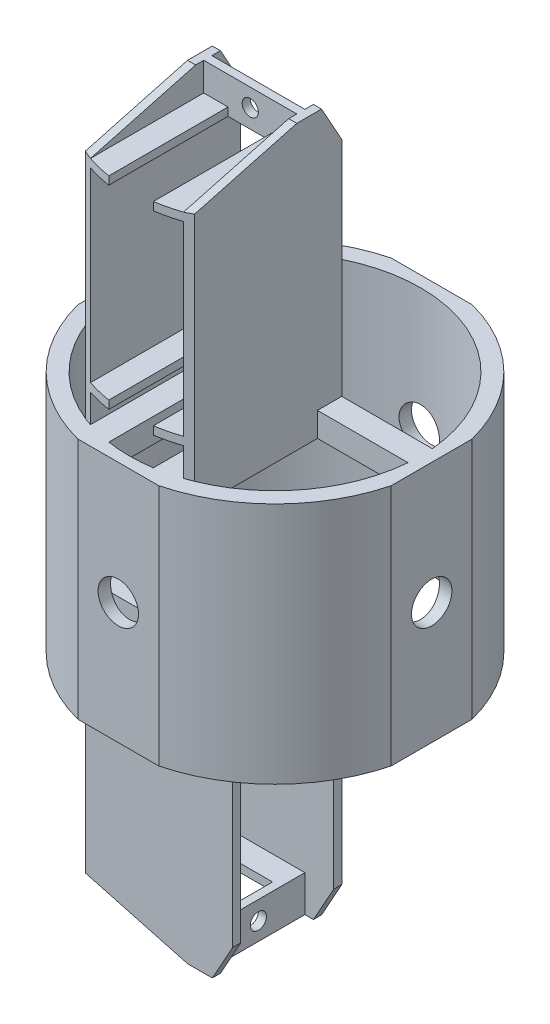
SolidWorks part; units mm, degrees
material "聚脂树脂"
ref_plane "前视基准面" through (0, 0, 0) normal (0, 0, 1) x (1, 0, 0)
ref_plane "上视基准面" through (0, 0, 0) normal (0, 1, 0) x (1, 0, 0)
ref_plane "右视基准面" through (0, 0, 0) normal (1, 0, 0) x (0, 0, -1)
other "Configuration Table"
sketch "草图3" plane through (0, 0, 0) normal (0, 1, 0) x (1, 0, 0)
  circle A0 centre (0, 0) radius 20
  circle A1 centre (0, 0) radius 18
  dimension "D1" = 40
  dimension "D2" = 36
extrude "凸台-拉伸2" add sketch "草图3" along normal blind 30
sketch "草图5" plane through (0, 0, 0) normal (0, 1, 0) x (1, 0, 0)
  line L0 (-1000, 0) -> (49000, 0) construction
  line L1 (0, -1000) -> (0, 49000) construction
  line L2 (-19.3649, -5) -> (-19.3649, 5)
  line L3 (-707.1068, -707.1068) -> (34648.2323, 34648.2323) construction
  line L4 (707.1068, -707.1068) -> (-34648.2323, 34648.2323) construction
  line L5 (19.3649, -5) -> (19.3649, 5)
  line L6 (-5, 19.3649) -> (5, 19.3649)
  line L7 (-5, -19.3649) -> (5, -19.3649)
  circle A0 centre (0, 0) radius 18 construction
  circle A1 centre (0, 0) radius 20 construction
  circle A2 centre (0, 0) radius 18
  circle A3 centre (0, 0) radius 20
  point P13 (-19.3649, 0)
  dimension "D1" = 10
sketch "草图6" plane through (0, 0, 0) normal (0, 1, 0) x (1, 0, 0)
  line L0 (-1000, 0) -> (49000, 0) construction
  line L1 (0, -1000) -> (0, 49000) construction
  line L2 (-707.1068, -707.1068) -> (34648.2323, 34648.2323) construction
  line L3 (707.1068, -707.1068) -> (-34648.2323, 34648.2323) construction
  line L4 (-17.2916, -5) -> (-17.2916, 5)
  line L5 (-5, -17.2916) -> (5, -17.2916)
  line L6 (5, 17.2916) -> (-5, 17.2916)
  line L7 (17.2916, 5) -> (17.2916, -5)
  circle A0 centre (0, 0) radius 18 construction
  circle A1 centre (0, 0) radius 18
  circle A2 centre (0, 0) radius 20 construction
  circle A3 centre (0, 0) radius 20
  point P17 (-17.2916, 0)
  dimension "D1" = 10
sketch "草图11" plane through (0, 0, 0) normal (0, 0, 1) x (1, 0, 0)
  line L0 (20, 30) -> (-20, 0) construction
  line L1 (-20, 30) -> (20, 0) construction
  circle A0 centre (0, 15) radius 2.5
  dimension "D1" = 5
extrude "切除-拉伸5" cut sketch "草图11" against normal through all and the other way blind 40
sketch "草图12" plane through (0, 0, 0) normal (1, 0, 0) x (0, 0, -1)
  line L0 (20, 30) -> (-20, 0) construction
  line L1 (20, 0) -> (-20, 30) construction
  circle A0 centre (0, 15) radius 2.5
  dimension "D1" = 5
extrude "切除-拉伸6" cut sketch "草图12" against normal through all and the other way blind 40
sketch "草图22" plane through (0, 0, 0) normal (0, 1, 0) x (1, 0, 0)
  line L0 (0, -1000) -> (0, 49000) construction
  line L1 (-1.5, 0) -> (1.5, 0) construction
  line L2 (1.5, 17.9374) -> (1.5, -17.9374)
  line L3 (-1.5, 17.9374) -> (-1.5, -17.9374)
  circle A0 centre (0, 0) radius 18
  point P8 (0, 0)
  point P10 (1.5, 0)
  point P14 (-1.5, 0)
  dimension "D1" = 36
  dimension "D2" = 3
extrude "凸台-拉伸13" add sketch "草图22" along normal blind 3 contours L2 A0 L3 region at (0, 0, 0)
sketch "草图23" plane through (0, 0, 0) normal (0, 1, 0) x (1, 0, 0)
  line L0 (-1000, 0) -> (49000, 0) construction
  line L2 (1.5, 17.9374) -> (1.5, -17.9374) construction
  line L3 (1.5, 17.9374) -> (1.5, -17.9374)
  line L5 (-16.6864, -6.75) -> (1.5, -6.75)
  line L6 (-16.6864, 6.75) -> (1.5, 6.75)
  circle A0 centre (0, 0) radius 18
  point P12 (-16.6864, 0)
  dimension "D1" = 36
  dimension "D2" = 13.5
  dimension "D3" = 18.1864
  dimension "D4" = 13.5
extrude "凸台-拉伸14" add sketch "草图23" along normal blind 3 contours A0 L0 L3 L6 | L0 A0 L5 L3 region at (-8.0383, 0, -3.3366) region at (-8.0383, 0, 3.3366)
sketch "草图44" plane through (0, 0, 0) normal (0, 1, 0) x (1, 0, 0)
  line L0 (0, 1.5) -> (0, -1.5) construction
  line L1 (17.9374, 1.5) -> (-17.9374, 1.5)
  line L2 (-17.9374, -1.5) -> (17.9374, -1.5)
  arc A0 (-17.9374, 1.5) -> (-17.9374, -1.5) centre (0, 0) ccw
  arc A1 (17.9374, -1.5) -> (17.9374, 1.5) centre (0, 0) ccw
  point P5 (0, 0)
  point P9 (0, 1.5)
  point P12 (0, -1.5)
  dimension "D1" = 36
  dimension "D2" = 3
extrude "凸台-拉伸26" add sketch "草图44" against normal blind 3 from surface starting at face at (0, 30, 20)
sketch "草图45" plane through (0, 0, 0) normal (0, 1, 0) x (1, 0, 0)
  line L0 (0, -1000) -> (0, 49000) construction
  line L5 (-17.9374, 1.5) -> (17.9374, 1.5) construction
  line L6 (-6.75, 1.5) -> (6.75, 1.5)
  line L7 (6.75, -16.6864) -> (6.75, 1.5)
  line L8 (-6.75, -16.6864) -> (-6.75, 1.5)
  arc A0 (-6.75, -16.6864) -> (6.75, -16.6864) centre (0, 0) ccw
  point P9 (0, -16.6864)
  dimension "D1" = 13.5
  dimension "D2" = 18.1864
extrude "凸台-拉伸27" add sketch "草图45" against normal blind 3 from surface starting at face at (0, 30, -9.75)
sketch "草图54" plane through (0, 0, 0) normal (0, 1, 0) x (1, 0, 0)
  line L0 (0, -1000) -> (0, 49000) construction
  line L2 (-5.75, -17.0569) -> (-5.75, -3.0569)
  line L3 (-5.75, -3.0569) -> (5.75, -3.0569)
  line L4 (5.75, -3.0569) -> (5.75, -17.0569)
  line L5 (-6.75, -2.0569) -> (-6.75, -16.6864)
  line L6 (-6.75, -16.6864) -> (-6.75, -1.5) construction
  line L8 (6.75, -2.0569) -> (6.75, -16.6864)
  line L9 (6.75, -1.5) -> (6.75, -16.6864) construction
  line L11 (6.75, -2.0569) -> (-6.75, -2.0569)
  arc A0 (-6.75, -16.6864) -> (-5.75, -17.0569) centre (0, 0) ccw
  arc A1 (5.75, -17.0569) -> (6.75, -16.6864) centre (0, 0) ccw
  arc A2 (-6.75, -16.6864) -> (-5.75, -17.0569) centre (0, 0) ccw
  point P9 (0, -17.0569)
  dimension "D1" = 11.5
  dimension "D2" = 13.5
  dimension "D3" = 14
  dimension "D4" = 1
  dimension "D5" = 2.0569
extrude "凸台-拉伸32" add sketch "草图54" along normal blind 32 from surface contours L0 L3 L4 A1 L8 L11 | L3 L0 L11 L5 A0 L2 region at (-2.875, 0, 2.8924) region at (0.1645, 0, 2.5569) starting at face at (11.1953, 30, 7.0897)
sketch "草图55" plane through (0, 0, 0) normal (0, 0, 1) x (1, 0, 0)
  line L0 (-6.75, 62) -> (6.75, 30) construction
  line L1 (-6.75, 30) -> (6.75, 62) construction
  line L2 (0, 59.8) -> (0, 32.2) construction
  line L4 (5.75, 57.5) -> (-5.75, 57.5)
  line L5 (5.75, 57.5) -> (5.75, 34.5)
  line L6 (5.75, 34.5) -> (-5.75, 34.5)
  line L7 (-5.75, 57.5) -> (-5.75, 34.5)
  line L8 (5.75, 57.5) -> (-5.75, 34.5) construction
  line L9 (5.75, 34.5) -> (-5.75, 57.5) construction
  circle A0 centre (0, 59.8) radius 1
  circle A1 centre (0, 32.2) radius 1
  point P6 (0, 46)
  point P12 (0, 46)
  dimension "D4" = 2
  dimension "D5" = 2
  dimension "D1" = 27.6
  dimension "D2" = 23
  dimension "D3" = 11.5
extrude "切除-拉伸25" cut sketch "草图55" along normal blind 32
sketch "草图56" plane through (0, 0, 0) normal (0, 1, 0) x (1, 0, 0)
  line L0 (-2.0569, -6.75) -> (-16.6864, -6.75)
  line L1 (-16.6864, -6.75) -> (-1.5, -6.75) construction
  line L2 (0, 0) -> (-28.8356, 0) construction
  line L4 (-2.0569, -6.75) -> (-2.0569, 6.75)
  line L5 (-16.6864, 6.75) -> (-1.5, 6.75) construction
  line L6 (-17.0569, 5.75) -> (-3.0569, 5.75)
  line L7 (-3.0569, 5.75) -> (-3.0569, -5.75)
  line L8 (-3.0569, -5.75) -> (-17.0569, -5.75)
  line L9 (-2.0569, 6.75) -> (-16.6864, 6.75)
  arc A0 (-16.6864, 6.75) -> (-17.0569, 5.75) centre (0, 0) ccw
  arc A1 (-17.0569, -5.75) -> (-16.6864, -6.75) centre (0, 0) ccw
  point P13 (-17.0569, 0)
  dimension "D1" = 11.5
  dimension "D2" = 14
  dimension "D3" = 1
  dimension "D4" = 1
extrude "凸台-拉伸33" add sketch "草图56" against normal blind 32
sketch "草图57" plane through (0, 0, 0) normal (1, 0, 0) x (0, 0, -1)
  line L0 (6.75, 0) -> (-6.75, -32) construction
  line L1 (6.75, -32) -> (-6.75, 0) construction
  line L2 (0, -29.8) -> (0, -2.2) construction
  line L4 (-5.75, -4.5) -> (5.75, -4.5)
  line L5 (-5.75, -4.5) -> (-5.75, -27.5)
  line L6 (-5.75, -27.5) -> (5.75, -27.5)
  line L7 (5.75, -4.5) -> (5.75, -27.5)
  line L8 (-5.75, -4.5) -> (5.75, -27.5) construction
  line L9 (-5.75, -27.5) -> (5.75, -4.5) construction
  circle A0 centre (0, -2.2) radius 1
  circle A1 centre (0, -29.8) radius 1
  point P8 (0, -16)
  point P12 (0, -16)
  dimension "D4" = 2
  dimension "D5" = 2
  dimension "D1" = 27.6
  dimension "D2" = 23
  dimension "D3" = 11.5
extrude "切除-拉伸26" cut sketch "草图57" against normal blind 32
sketch "草图59" plane through (0, 0, 0) normal (0, 1, 0) x (1, 0, 0)
  line L0 (-6.75, -2.0569) -> (-6.75, 1.5)
  line L1 (-17.9374, 1.5) -> (17.9374, 1.5) construction
  line L2 (-6.75, 1.5) -> (-5.75, 1.5)
  line L3 (-5.75, 1.5) -> (-5.75, -2.0569)
  line L4 (-6.75, -2.0569) -> (6.75, -2.0569) construction
  line L5 (-5.75, -2.0569) -> (-6.75, -2.0569)
  line L6 (6.75, -2.0569) -> (6.75, 1.5)
  line L7 (6.75, 1.5) -> (5.75, 1.5)
  line L8 (5.75, 1.5) -> (5.75, -2.0569)
  line L9 (6.75, -2.0569) -> (5.75, -2.0569)
  dimension "D1" = 1
  dimension "D2" = 1
extrude "凸台-拉伸34" add sketch "草图59" along normal up to surface (62 mm away) from surface up to face at (0, 62, 9.7161) starting at face at (0, 30, 7.2412)
sketch "草图60" plane through (0, 0, 0) normal (0, 1, 0) x (1, 0, 0)
  line L0 (-2.0569, -6.75) -> (1.5, -6.75)
  line L1 (1.5, 17.9374) -> (1.5, -17.9374) construction
  line L2 (1.5, -6.75) -> (1.5, -5.75)
  line L3 (1.5, -5.75) -> (-2.0569, -5.75)
  line L4 (-2.0569, -6.75) -> (-2.0569, 6.75) construction
  line L5 (-2.0569, -5.75) -> (-2.0569, -6.75)
  line L6 (-2.0569, 6.75) -> (1.5, 6.75)
  line L7 (1.5, 6.75) -> (1.5, 5.75)
  line L8 (1.5, 5.75) -> (-2.0569, 5.75)
  line L9 (-2.0569, 5.75) -> (-2.0569, 6.75)
  dimension "D1" = 1
  dimension "D2" = 1
extrude "凸台-拉伸35" add sketch "草图60" against normal up to surface (32 mm away) from surface up to face at (-9.7161, -32, 0) starting at face at (-7.2412, 0, 0)
sketch "草图62" plane through (0, 0, 0) normal (1, 0, 0) x (0, 0, -1)
  line L0 (1.5, 62) -> (1.5, 57.5)
  line L1 (1.5, 62) -> (1.5, 30) construction
  line L2 (1.5, 57.5) -> (-1, 62)
  line L3 (-16.6864, 62) -> (1.5, 62) construction
  line L4 (-1, 62) -> (1.5, 62)
  line L5 (-17.0569, 62) -> (-4.0569, 62)
  line L6 (-4.0569, 62) -> (-17.0569, 58.5)
  line L7 (-17.0569, 62) -> (-17.0569, 30) construction
  line L8 (-17.0569, 58.5) -> (-17.0569, 62)
  dimension "D1" = 2.5
  dimension "D2" = 4.5
  dimension "D3" = 3.5
  dimension "D4" = 13
extrude "切除-拉伸27" cut sketch "草图62" against normal through all and the other way through all contours L8 L5 L6 | L4 L0 L2
sketch "草图63" plane through (0, 0, 0) normal (0, 0, 1) x (1, 0, 0)
  line L0 (1.5, -32) -> (1.5, -27.5)
  line L1 (1.5, -32) -> (1.5, 0) construction
  line L2 (1.5, -27.5) -> (-1, -32)
  line L3 (-16.6864, -32) -> (1.5, -32) construction
  line L4 (-1, -32) -> (1.5, -32)
  line L5 (-17.0569, -32) -> (-4.0569, -32)
  line L6 (-4.0569, -32) -> (-17.0569, -28.5)
  line L7 (-17.0569, -32) -> (-17.0569, 0) construction
  line L8 (-17.0569, -28.5) -> (-17.0569, -32)
  dimension "D1" = 4.5
  dimension "D2" = 2.5
  dimension "D3" = 13
  dimension "D4" = 3.5
extrude "切除-拉伸28" cut sketch "草图63" against normal through all and the other way through all
sketch "草图64" plane through (0, 0, 0) normal (0, 1, 0) x (1, 0, 0)
  line L0 (-5.75, -3.0569) -> (-2.75, -3.0569)
  line L1 (5.75, -3.0569) -> (-5.75, -3.0569) construction
  line L2 (-2.75, -3.0569) -> (-2.75, -17.7887)
  line L3 (-5.75, -3.0569) -> (-5.75, -17.0569)
  line L4 (5.75, -17.0569) -> (5.75, -3.0569)
  line L5 (5.75, -3.0569) -> (2.75, -3.0569)
  line L6 (5.75, -3.0569) -> (-5.75, -3.0569) construction
  line L7 (2.75, -3.0569) -> (2.75, -17.7887)
  arc A0 (-5.75, -17.0569) -> (-2.75, -17.7887) centre (0, 0) ccw
  arc A1 (2.75, -17.7887) -> (5.75, -17.0569) centre (0, 0) ccw
  dimension "D1" = 3
  dimension "D2" = 3
extrude "凸台-拉伸36" add sketch "草图64" against normal blind 1 from surface contours L3 A0 L2 L0 | L4 L5 L7 A1 starting at face at (0, 34.5, 2.5569)
sketch "草图65" plane through (0, 0, 0) normal (0, 1, 0) x (1, 0, 0)
  line L0 (-17.0569, -5.75) -> (-3.0569, -5.75)
  line L1 (-3.0569, -5.75) -> (-3.0569, -2.75)
  line L2 (-3.0569, 5.75) -> (-3.0569, -5.75) construction
  line L3 (-3.0569, -2.75) -> (-17.7887, -2.75)
  line L4 (-17.0569, 5.75) -> (-3.0569, 5.75)
  line L5 (-3.0569, 5.75) -> (-3.0569, 2.75)
  line L6 (-3.0569, 2.75) -> (-17.7887, 2.75)
  arc A0 (-17.7887, -2.75) -> (-17.0569, -5.75) centre (0, 0) ccw
  arc A1 (-17.0569, 5.75) -> (-17.7887, 2.75) centre (0, 0) ccw
  dimension "D1" = 3
  dimension "D2" = 3
extrude "凸台-拉伸37" add sketch "草图65" along normal blind 1 from surface starting at face at (-2.5569, -4.5, 0)
sketch "草图66" plane through (0, 0, 0) normal (0, 1, 0) x (1, 0, 0)
  line L0 (-5.75, -3.0569) -> (5.75, -3.0569)
  line L1 (5.75, -3.0569) -> (5.75, -17.0569)
  line L2 (-5.75, -3.0569) -> (-5.75, -17.0569)
  arc A0 (-5.75, -17.0569) -> (5.75, -17.0569) centre (0, 0) ccw
extrude "凸台-拉伸38" add sketch "草图66" along normal blind 1 from surface starting at face at (0, 57.5, 2.5569)
sketch "草图67" plane through (0, 0, 0) normal (0, 1, 0) x (1, 0, 0)
  line L0 (-17.0569, -5.75) -> (-3.0569, -5.75)
  line L1 (-17.0569, -5.75) -> (-2.0569, -5.75) construction
  line L2 (-17.0569, -5.75) -> (-4.0569, -5.75) construction
  line L3 (-3.0569, -5.75) -> (-3.0569, 5.75)
  line L4 (-3.0569, 5.75) -> (-17.0569, 5.75)
  arc A0 (-17.0569, 5.75) -> (-17.0569, -5.75) centre (0, 0) ccw
extrude "凸台-拉伸39" add sketch "草图67" against normal blind 1 from surface starting at face at (-2.5569, -27.5, 0)
sketch "草图68" plane through (0, 0, 0) normal (0, 1, 0) x (1, 0, 0)
  line L1 (5.75, -3.0569) -> (-5.75, -3.0569) construction
  line L2 (2.75, -3.0569) -> (-2.75, -3.0569)
  arc A0 (-2.75, -3.0569) -> (2.75, -3.0569) centre (0, -3.0569) ccw
  dimension "D1" = 5.5
extrude "切除-拉伸29" cut sketch "草图68" against normal blind 1 from surface starting at face at (0, 58.5, 10.2927)
sketch "草图69" plane through (0, 0, 0) normal (0, 1, 0) x (1, 0, 0)
  line L1 (-3.0569, 5.75) -> (-3.0569, -5.75) construction
  line L2 (-3.0569, -2.75) -> (-3.0569, 2.75)
  arc A0 (-3.0569, 2.75) -> (-3.0569, -2.75) centre (-3.0569, 0) ccw
  dimension "D1" = 5.5
extrude "切除-拉伸30" cut sketch "草图69" along normal blind 1 from surface starting at face at (-10.2927, -28.5, 0)
sketch "草图70" plane through (0, 0, 0) normal (0, 1, 0) x (1, 0, 0)
  line L0 (-2.75, -3.0569) -> (-2.75, -17.7887)
  line L1 (-2.75, -3.0569) -> (2.75, -3.0569)
  line L2 (2.75, -3.0569) -> (2.75, -17.7887)
  arc A0 (-2.75, -17.7887) -> (2.75, -17.7887) centre (0, 0) ccw
extrude "切除-拉伸31" cut sketch "草图70" against normal blind 3 from surface starting at face at (0, 30, 0.2784)
sketch "草图71" plane through (0, 0, 0) normal (0, 1, 0) x (1, 0, 0)
  line L0 (-17.7887, 2.75) -> (-3.0569, 2.75)
  line L1 (-3.0569, 2.75) -> (-3.0569, -2.75)
  line L2 (-3.0569, 5.75) -> (-3.0569, -5.75) construction
  line L3 (-3.0569, -2.75) -> (-17.7887, -2.75)
  arc A0 (-17.7887, 2.75) -> (-17.7887, -2.75) centre (0, 0) ccw
  arc A1 (-3.0569, 2.75) -> (-3.0569, -2.75) centre (-3.0569, 0) ccw construction
extrude "切除-拉伸32" cut sketch "草图71" along normal blind 3
sketch "草图74" plane through (0, 0, 0) normal (0, 1, 0) x (1, 0, 0)
  line L0 (-2.75, -3.0569) -> (-2.75, -17.7887)
  line L1 (-2.75, -3.0569) -> (2.75, -3.0569)
  line L2 (2.75, -3.0569) -> (2.75, -17.7887)
  arc A0 (-2.75, -17.7887) -> (2.75, -17.7887) centre (0, 0) ccw
  arc A1 (-2.75, -3.0569) -> (2.75, -3.0569) centre (0, -3.0569) ccw construction
extrude "切除-拉伸33" cut sketch "草图74" against normal blind 3 from surface starting at face at (0, 58.5, 8.3391)
sketch "草图75" plane through (0, 0, 0) normal (0, 1, 0) x (1, 0, 0)
  line L0 (-3.0569, -2.75) -> (-17.7887, -2.75)
  line L1 (-3.0569, -2.75) -> (-3.0569, 2.75)
  line L2 (-3.0569, 2.75) -> (-17.7887, 2.75)
  arc A0 (-17.7887, 2.75) -> (-17.7887, -2.75) centre (0, 0) ccw
extrude "切除-拉伸34" cut sketch "草图75" along normal blind 3 from surface starting at face at (-8.3391, -28.5, 0)
extrude "切除-拉伸35" cut sketch "草图5" along normal through all contours L6 A3 | L2 A3 | L7 A3 | L5 A3 region at (-19.6193, 0, 0) region at (0, 0, 19.6193) region at (0, 0, -19.6193) region at (19.6193, 0, 0)
